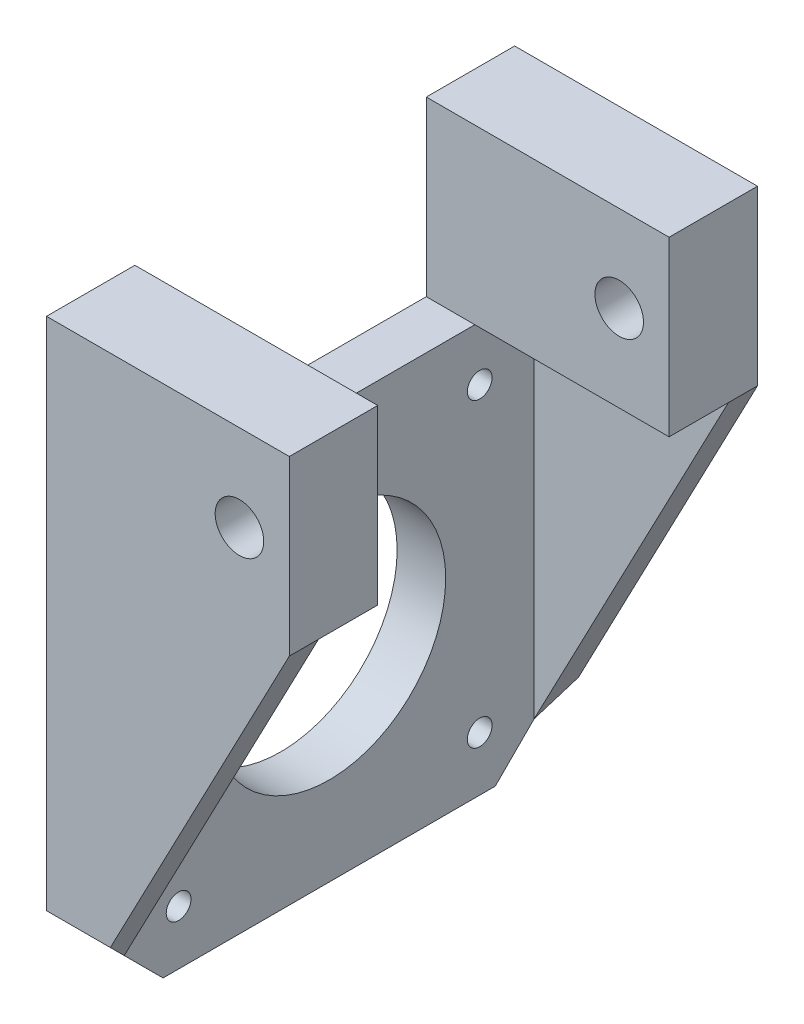
SolidWorks part; units mm, degrees
ref_plane "Front Plane" through (0, 0, 0) normal (0, 0, 1) x (1, 0, 0)
ref_plane "Top Plane" through (0, 0, 0) normal (0, 1, 0) x (1, 0, 0)
ref_plane "Right Plane" through (0, 0, 0) normal (1, 0, 0) x (0, 0, -1)
sketch "Sketch1" plane through (0, 0, 0) normal (1, 0, 0) x (0, 0, -1)
  line L0 (-0.3826, 8.0214) -> (-6.4826, 8.0214)
  line L1 (-6.4826, 8.0214) -> (-9.3826, 8.0214)
  line L2 (-9.3826, 8.0214) -> (-9.3826, -34.1786)
  line L3 (-9.3826, -34.1786) -> (-4.3816, -34.1786)
  line L4 (-4.3816, -34.1786) -> (-0.3826, -30.1796)
  line L5 (-0.3826, -30.1796) -> (-0.3826, 8.0214)
  line L6 (-6.4826, 25.8214) -> (-6.4826, 8.0214)
  line L7 (-6.4826, 8.0214) -> (-0.3826, 8.0214)
  line L8 (-0.3826, 8.0214) -> (2.6174, 8.0214)
  line L9 (2.6174, 8.0214) -> (2.6174, 25.8214)
  line L10 (2.6174, 25.8214) -> (-6.4826, 25.8214)
  circle A0 centre (-5.9826, -28.5786) radius 1.275
  circle A1 centre (-5.9826, 2.4214) radius 1.275
extrude "Boss-Extrude1" add sketch "Sketch1" along normal blind 5 contours L4 L5 L0 L1 L2 L3 A1 A0 | L9 L10 L6 L0 L8 region at (0, -12.6414, 4.9216) region at (0, 16.9214, 1.9326)
sketch "Sketch2" plane through (5, 0, 0) normal (1, 0, 0) x (0, 0, -1)
  line L1 (-6.4826, 25.8214) -> (2.6174, 25.8214)
  line L2 (-6.4826, 25.8214) -> (-6.4826, 8.0214)
  line L3 (-6.4826, 8.0214) -> (2.6174, 8.0214)
  line L4 (2.6174, 25.8214) -> (2.6174, 8.0214)
extrude "Boss-Extrude2" add sketch "Sketch2" along normal blind 20
sketch "Sketch3" plane through (0, 0, 0.3826) normal (0, 0, -1) x (-1, 0, 0)
  line L1 (-25, 8.0214) -> (0, 8.0214)
  line L2 (0, 8.0214) -> (0, -30.1796)
  line L3 (0, -30.1796) -> (-5, -30.1796)
  line L4 (-5, -30.1796) -> (-25, 8.0214)
extrude "Boss-Extrude3" add sketch "Sketch3" along normal blind 3
sketch "Sketch4" plane through (5, 0, 0) normal (1, 0, 0) x (0, 0, -1)
  line L0 (-0.3826, -30.1796) -> (2.6174, -27.1796)
  line L1 (2.6174, 8.0214) -> (2.6174, -30.1796) construction
  line L2 (2.6174, -27.1796) -> (2.6174, -30.1796)
  line L3 (2.6174, -30.1796) -> (-0.3826, -30.1796)
extrude "Cut-Extrude1" cut sketch "Sketch4" against normal mid plane 30
sketch "Sketch5" plane through (0, 0, -2.6174) normal (0, 0, -1) x (-1, 0, 0)
  circle A0 centre (-19.8627, 16.9214) radius 2.5
extrude "Cut-Extrude2" cut sketch "Sketch5" against normal mid plane 30 contours A0 region at (19.8627, 16.9214, -2.6174)
ref_plane "Plane2" through (0, 0, 21.4826) normal (0, 0, 1) x (1, 0, 0)
mirror "Mirror14" about plane through (0, 0, 21.4826) normal (0, 0, 1) of bodies 106
sketch "Sketch7" plane through (5, 0, 0) normal (1, 0, 0) x (0, 0, -1)
  line L1 (-33.5826, 8.0214) -> (-9.3826, 8.0214)
  line L2 (-33.5826, 8.0214) -> (-33.5826, -34.1786)
  line L3 (-33.5826, -34.1786) -> (-9.3826, -34.1786)
  line L4 (-9.3826, 8.0214) -> (-9.3826, -34.1786)
extrude "Boss-Extrude4" add sketch "Sketch7" against normal blind 5
sketch "Sketch8" plane through (5, 0, 0) normal (1, 0, 0) x (0, 0, -1)
  circle A0 centre (-21.4826, -13.0786) radius 12
extrude "Cut-Extrude3" cut sketch "Sketch8" against normal blind 5
